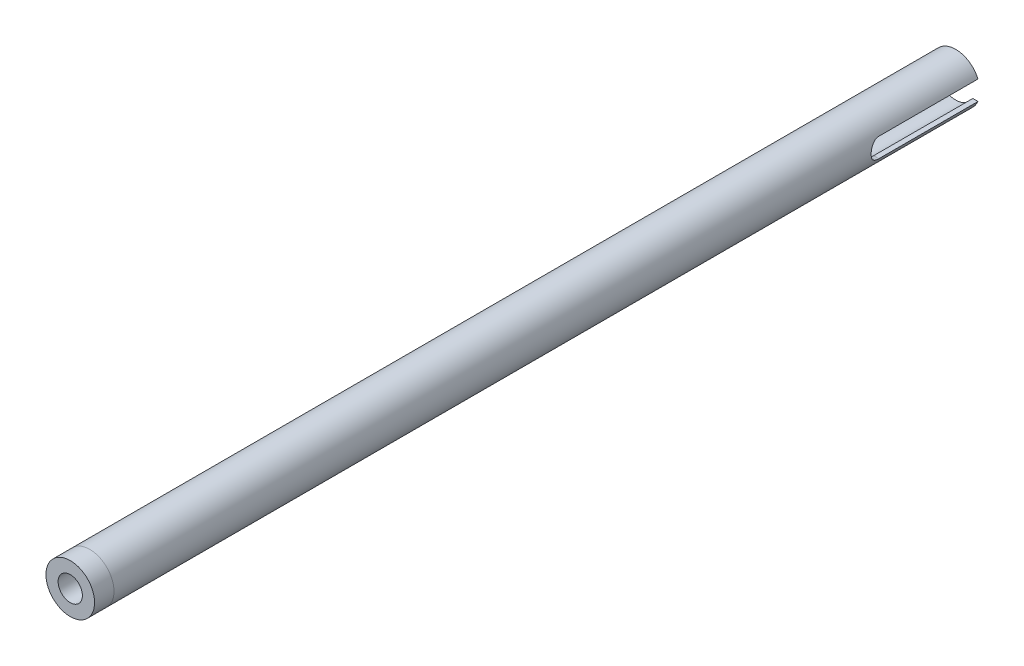
SolidWorks part; units mm, degrees
ref_plane "Front Plane" through (0, 0, 0) normal (0, 0, 1) x (1, 0, 0)
ref_plane "Top Plane" through (0, 0, 0) normal (0, 1, 0) x (1, 0, 0)
ref_plane "Right Plane" through (0, 0, 0) normal (1, 0, 0) x (0, 0, -1)
sketch "Axis" plane through (0, 0, 0) normal (0, 1, 0) x (1, 0, 0)
  line L0 (0, 0) -> (0, 289.2171) construction
  line L1 (0, 0) -> (0, -34.925) construction
  line L2 (0, 289.2171) -> (-7.9375, 289.2171) construction
  line L3 (0, 315.4109) -> (-28.3585, 221.8279) construction
  dimension "D1" = 34.925
  dimension "D2" = 7.9375
sketch "Sketch1" plane through (0, 0, 0) normal (0, 0, 1) x (1, 0, 0)
  line L0 (-7.9375, 0) -> (7.9375, 0) construction
  line L1 (-7.2748, 3.175) -> (7.2748, 3.175)
  line L2 (-7.2748, -3.175) -> (7.2748, -3.175)
  circle A0 centre (0, 0) radius 7.9375
  circle A1 centre (0, 0) radius 6.4135
  circle A2 centre (0, 0) radius 3.9688
  dimension "D1" = 15.875
  dimension "D3" = 7.9375
  dimension "D2" = 1.524
  dimension "D4" = 6.35
extrude "Threaded insert 1-1" add sketch "Sketch1" against normal blind 6.35 contours A2 L1 A1 | A1 L1 A0 | A2 L0 A1 L1 | A1 L0 A0 L1 | L0 A1 L2 A0 | L0 A2 L2 A1 | A2 L2 A1 | A1 L2 A0 | L0 A1 L2 A2 | L0 A0 L2 A1 | A0 L0 A1 L1 | A1 L0 A2 L1 region at (4.7887, 1.6543, 0) region at (4.7887, -1.6543, 0) region at (6.9234, 1.6163, 0) region at (6.9234, -1.6163, 0) region at (-4.7887, -1.6543, 0) region at (-4.7887, 1.6543, 0) region at (0, 4.6159, 0) region at (0, -4.6159, 0) region at (0, 6.5666, 0) region at (6.4237, -3.3281, 0) region at (-6.9234, -1.6163, 0) region at (-6.9234, 1.6163, 0)
extrude "Threaded insert 1-2" add sketch "Sketch1<3>" against normal blind 9.525 from surface contours A2 L1 A1 | A2 L0 A1 L1 | L0 A2 L2 A1 | A2 L2 A1 | L0 A1 L2 A2 | A1 L0 A2 L1 region at (4.7887, 1.6543, 0) region at (4.7887, -1.6543, 0) region at (-4.7887, -1.6543, 0) region at (-4.7887, 1.6543, 0) region at (0, 4.6159, 0) region at (0, -4.6159, 0) starting at face at (7.9375, 0, -6.35)
sketch "Sketch1<3>" plane through (0, 0, 0) normal (0, 0, 1) x (1, 0, 0) same geometry as "Sketch1"
extrude "A-arm tube" add sketch "Sketch1<4>" against normal up to vertex (289.2171 mm away) from surface separate body contours A1 L1 A0 | A1 L0 A0 L1 | L0 A1 L2 A0 | A1 L2 A0 | L0 A0 L2 A1 | A0 L0 A1 L1 region at (6.9234, 1.6163, 0) region at (6.9234, -1.6163, 0) region at (0, 6.5666, 0) region at (6.4237, -3.3281, 0) region at (-6.9234, -1.6163, 0) region at (-6.9234, 1.6163, 0) up to point (0, 0, -289.2171) starting at face at (6.4135, 0, -6.35)
sketch "Sketch1<4>" plane through (0, 0, 0) normal (0, 0, 1) x (1, 0, 0) same geometry as "Sketch1"
extrude "Apex slot" cut sketch "Sketch1<5>" along normal blind 35.56 from surface contours A0 L0 A1 L1 | L0 A0 L2 A1 | A1 L0 A0 L1 | L0 A1 L2 A0 region at (6.9234, 1.6163, 0) region at (6.9234, -1.6163, 0) region at (-6.9234, -1.6163, 0) region at (-6.9234, 1.6163, 0) starting at face at (6.4135, 0, -289.2171)
sketch "Sketch1<5>" plane through (0, 0, 0) normal (0, 0, 1) x (1, 0, 0) same geometry as "Sketch1"
fillet "Fillet1" radius 3.175 4 edges at (-6.4237, 3.175, -253.6571) (-6.4237, -3.175, -253.6571) (6.4237, -3.175, -253.6571) (6.4237, 3.175, -253.6571)
equation "\"tube diameter\"= 5 / 8"
equation "\"tube thickness\"= .06"
equation "\"apex thickness\"= .25"
equation "\"tube slot\"= 1.4"
equation "\"D1@Sketch1\"=\"tube diameter\""
equation "\"D2@Sketch1\"=\"tube thickness\""
equation "\"threaded insert hole\"= .3125"
equation "\"D3@Sketch1\"=\"threaded insert hole\""
equation "\"D4@Sketch1\"=\"apex thickness\""
equation "\"D1@Apex slot\" = \"tube slot\""
equation "\"D1@Fillet1\"=\"apex thickness\"/2"
equation "\"D2@Axis\"=\"tube diameter\"/2"
